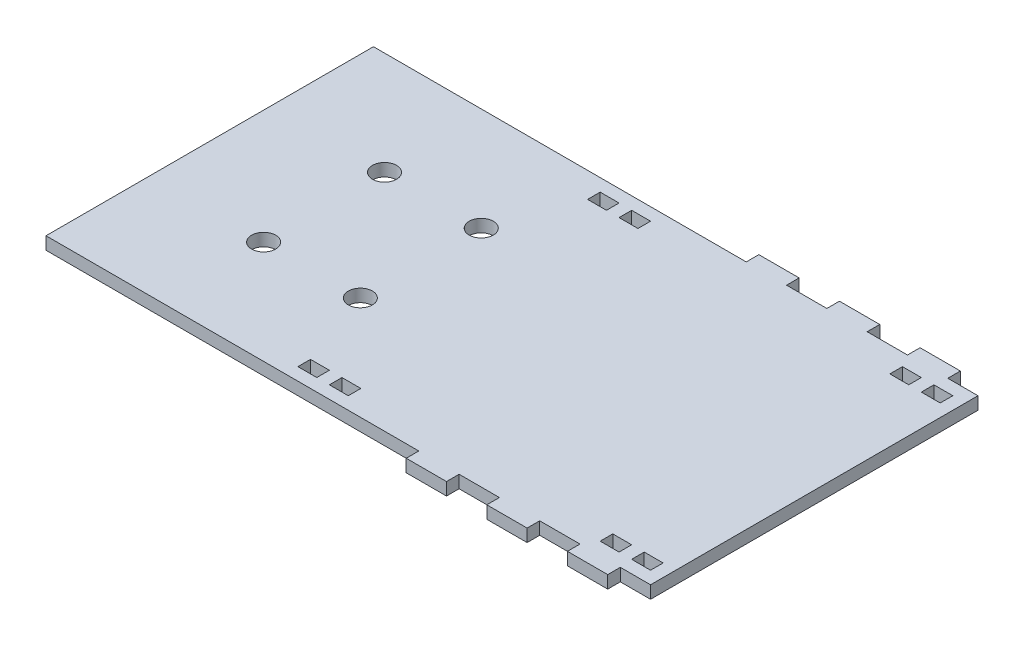
SolidWorks part; units mm, degrees
ref_plane "Front Plane" through (0, 0, 0) normal (0, 0, 1) x (1, 0, 0)
ref_plane "Top Plane" through (0, 0, 0) normal (0, 1, 0) x (1, 0, 0)
ref_plane "Right Plane" through (0, 0, 0) normal (1, 0, 0) x (0, 0, -1)
sketch "Sketch1" plane through (0, 0, 0) normal (0, 1, 0) x (1, 0, 0)
  line L0 (38.1, -41.275) -> (48.26, -41.275)
  line L1 (76.2, -41.275) -> (-76.2, -41.275)
  line L2 (76.2, -41.275) -> (76.2, 41.275)
  line L3 (76.2, 41.275) -> (-76.2, 41.275)
  line L4 (-76.2, -41.275) -> (-76.2, 41.275)
  line L5 (76.2, -41.275) -> (-76.2, 41.275) construction
  line L6 (76.2, 41.275) -> (-76.2, -41.275) construction
  line L7 (58.42, -41.275) -> (68.58, -41.275)
  line L8 (58.42, -41.275) -> (58.42, -44.45)
  line L9 (58.42, -44.45) -> (68.58, -44.45)
  line L10 (68.58, -41.275) -> (68.58, -44.45)
  line L11 (38.1, -41.275) -> (38.1, -44.45)
  line L12 (38.1, -44.45) -> (48.26, -44.45)
  line L13 (48.26, -41.275) -> (48.26, -44.45)
  line L14 (17.78, -41.275) -> (27.94, -41.275)
  line L15 (17.78, -41.275) -> (17.78, -44.45)
  line L16 (17.78, -44.45) -> (27.94, -44.45)
  line L17 (27.94, -41.275) -> (27.94, -44.45)
  line L18 (58.42, 44.45) -> (68.58, 44.45)
  line L19 (58.42, 44.45) -> (58.42, 41.275)
  line L20 (58.42, 41.275) -> (68.58, 41.275)
  line L21 (68.58, 44.45) -> (68.58, 41.275)
  line L22 (38.1, 44.45) -> (48.26, 44.45)
  line L23 (38.1, 44.45) -> (38.1, 41.275)
  line L24 (38.1, 41.275) -> (48.26, 41.275)
  line L25 (48.26, 44.45) -> (48.26, 41.275)
  line L26 (17.78, 44.45) -> (27.94, 44.45)
  line L27 (17.78, 44.45) -> (17.78, 41.275)
  line L28 (17.78, 41.275) -> (27.94, 41.275)
  line L29 (27.94, 44.45) -> (27.94, 41.275)
  line L30 (58.42, -41.275) -> (38.1, -41.275) construction
  point P0 (0, 0)
  dimension "D1" = 3.175
  dimension "D2" = 10.16
  dimension "D5" = 20.32
  dimension "D6" = 82.55
  dimension "D7" = 152.4
  dimension "D8" = 7.62
  dimension "D3" = 3
  dimension "D4" = 2
extrude "Boss-Extrude1" add sketch "Sketch1" along normal blind 3.175 contours L17 L1 L15 L16 | L4 L1 L0 L2 L3 | L13 L0 L11 L12 | L29 L26 L27 L3 | L10 L9 L8 L7 | L18 L21 L20 L19 | L22 L25 L24 L23 region at (0, 0, 0) region at (43.18, 0, 42.8625) region at (22.86, 0, 42.8625) region at (22.86, 0, -42.8625)
sketch "Sketch2" plane through (0, 3.175, 0) normal (0, 1, 0) x (1, 0, 0)
  line L0 (-47.3754, 15.24) -> (-47.3754, -15.24) construction
  line L1 (-47.3754, 0) -> (-76.2, 0) construction
  line L2 (-76.2, -41.275) -> (-76.2, 41.275) construction
  circle A0 centre (-47.3754, 15.24) radius 3.039
  circle A1 centre (-22.9914, 15.24) radius 3.039
  circle A2 centre (-22.9914, -15.24) radius 3.039
  circle A3 centre (-47.3754, -15.24) radius 3.039
  dimension "D4" = 24.384
  dimension "D3" = 30.48
  dimension "D1" = 2
  dimension "D2" = 2
extrude "Caster Mounting Holes" cut sketch "Sketch2" against normal through all
sketch "Sketch3" plane through (0, 3.175, 0) normal (0, 1, 0) x (1, 0, 0)
  line L0 (58.42, 41.275) -> (48.26, 41.275) construction
  line L2 (65.0875, 38.1) -> (65.0875, 34.925)
  line L4 (68.2625, 38.1) -> (68.2625, 34.925)
  line L7 (76.2, -41.275) -> (76.2, 41.275) construction
  line L9 (68.2625, 38.1) -> (73.025, 38.1)
  line L10 (73.025, 38.1) -> (73.025, 34.925)
  line L11 (73.025, 34.925) -> (68.2625, 34.925)
  line L15 (65.0875, 34.925) -> (60.325, 34.925)
  line L16 (60.325, 34.925) -> (60.325, 38.1)
  line L17 (60.325, 38.1) -> (65.0875, 38.1)
  point P0 (66.675, 36.5125)
  dimension "D1" = 3.175
  dimension "D2" = 4.7625
  dimension "D3" = 3.175
  dimension "D4" = 3.175
  dimension "D5" = 3.175
extrude "Cut-Extrude1" cut sketch "Sketch3" against normal through all contours L17 L16 L15 L2 | L11 L10 L9 L4 region at (62.7063, 3.175, -36.5125) region at (70.6438, 3.175, -36.5125)
pattern_linear "LPattern1" count 2 spacing 76.2 along (-1, 0, 0) count 2 spacing 73.025 along (0, 0, 1) of "Cut-Extrude1"
